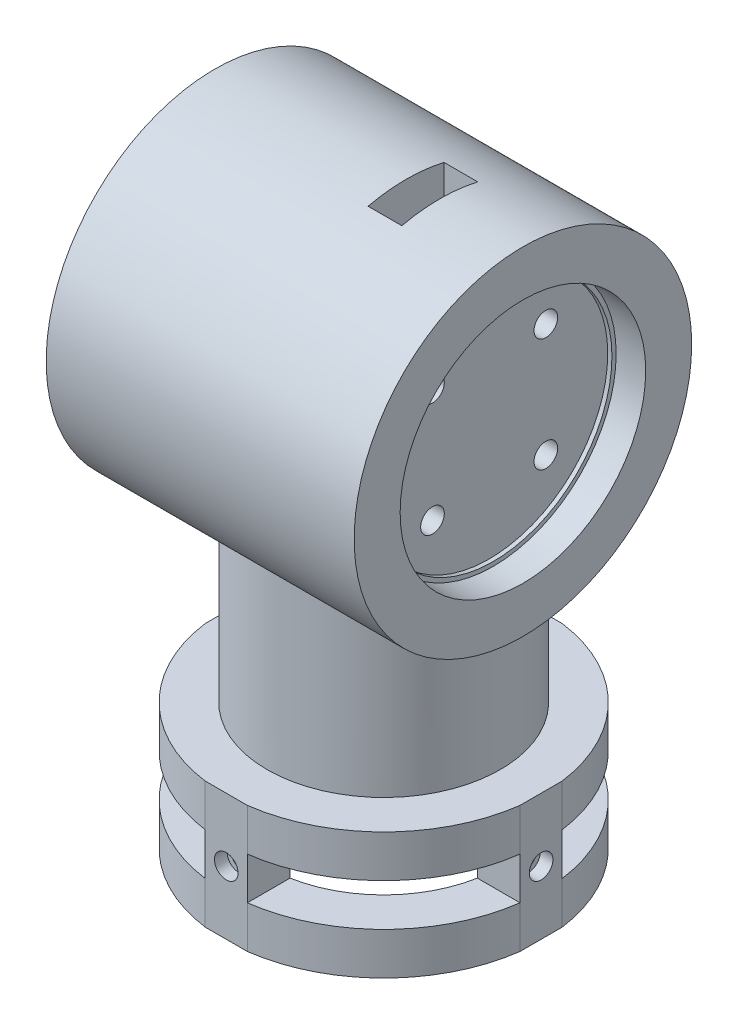
SolidWorks part; units mm, degrees
ref_plane "前视基准面" through (0, 0, 0) normal (0, 0, 1) x (1, 0, 0)
ref_plane "上视基准面" through (0, 0, 0) normal (0, 1, 0) x (1, 0, 0)
ref_plane "右视基准面" through (0, 0, 0) normal (1, 0, 0) x (0, 0, -1)
sketch "草图1" plane through (0, 0, 0) normal (0, 1, 0) x (1, 0, 0)
  circle A0 centre (0, 0) radius 27.65
  circle A2 centre (0, 0) radius 17.65
extrude "凸台-拉伸1" add sketch "草图1" along normal blind 100
sketch "草图9" plane through (0, 0, 0) normal (0, 1, 0) x (1, 0, 0)
  circle A0 centre (0, 0) radius 27.65
  circle A1 centre (0, 0) radius 37.65
extrude "凸台-拉伸6" add sketch "草图9" along normal blind 30
sketch "草图16" plane through (0, 0, 0) normal (1, 0, 0) x (0, 0, -1)
  line L0 (27.65, 100) -> (-27.65, 100) construction
  circle A0 centre (0, 100) radius 28.5
  circle A1 centre (0, 100) radius 40
extrude "凸台-拉伸8" add sketch "草图16" along normal blind 40 and the other way blind 40
sketch "草图17" plane through (0, 0, 0) normal (1, 0, 0) x (0, 0, -1)
  line L0 (27.65, 100) -> (-27.65, 100) construction
  circle A0 centre (0, 100) radius 28.5
extrude "切除-拉伸5" cut sketch "草图17" against normal through all both and the other way through all
sketch "草图19" plane through (0, 0, 0) normal (0, -1, 0) x (1, 0, 0)
  circle A0 centre (0, 0) radius 17.65
extrude "切除-拉伸6" cut sketch "草图19" against normal up to next and the other way through all
sketch "草图20" plane through (0, 0, 0) normal (1, 0, 0) x (0, 0, -1)
  circle A0 centre (0, 100) radius 28.5
extrude "凸台-拉伸9" add sketch "草图20" along normal blind 16.7 from offset 13.3
sketch "草图21" plane through (0, 0, 0) normal (0, 1, 0) x (1, 0, 0)
  line L0 (40, 0) -> (40, 9) construction
  line L1 (40, 9) -> (13.3, 9) construction
  line L4 (0, 0) -> (40, 0) construction
  line L9 (40, -40) -> (40, 40) construction
  line L17 (13.3, 9) -> (5.3, 9)
  line L18 (13.3, 9) -> (13.3, -9)
  line L19 (13.3, -9) -> (5.3, -9)
  line L20 (5.3, 9) -> (5.3, -9)
  dimension "D1" = 26.7
  dimension "D2" = 8
  dimension "D3" = 18
extrude "切除-拉伸7" cut sketch "草图21" along normal up to next
sketch "草图24" plane through (0, 0, 0) normal (1, 0, 0) x (0, 0, -1)
  circle A0 centre (0, 100) radius 28.5
  circle A1 centre (0, 100) radius 28
extrude "凸台-拉伸10" add sketch "草图24" along normal up to surface (40 mm away) from surface up to face at (40, 100, -40) starting at face at (30, 100, -28.5)
sketch "草图25" plane through (40, 0, 0) normal (1, 0, 0) x (0, 0, -1)
  circle A0 centre (0, 100) radius 40
extrude "切除-拉伸8" cut sketch "草图25" against normal blind 7
sketch "草图26" plane through (0, 0, 0) normal (0, 1, 0) x (1, 0, 0)
  line L0 (-5, 5) -> (-27.1942, 5) construction
  line L1 (-5, -5) -> (5, -5) construction
  line L2 (-5, -5) -> (-5, 5) construction
  line L3 (-5, 5) -> (5, 5) construction
  line L4 (5, -5) -> (5, 5) construction
  line L5 (-5, -5) -> (5, 5) construction
  line L6 (-5, 5) -> (5, -5) construction
  line L7 (-27.1942, 5) -> (-37.3165, 5)
  line L8 (-5, 5) -> (-5, 27.1942) construction
  line L9 (-5, 27.1942) -> (-5, 37.3165)
  line L10 (5, 5) -> (5, 27.1942) construction
  line L11 (5, 27.1942) -> (5, 37.3165)
  line L12 (5, 5) -> (27.1942, 5) construction
  line L13 (27.1942, 5) -> (37.3165, 5)
  line L14 (-5, -5) -> (-27.1942, -5) construction
  line L15 (-27.1942, -5) -> (-37.3165, -5)
  line L16 (-5, -5) -> (-5, -27.1942) construction
  line L17 (-5, -27.1942) -> (-5, -37.3165)
  line L18 (5, -5) -> (5, -27.1942) construction
  line L19 (5, -27.1942) -> (5, -37.3165)
  line L20 (5, -5) -> (27.1942, -5) construction
  line L21 (27.1942, -5) -> (37.3165, -5)
  arc A0 (-37.3165, -5) -> (-5, -37.3165) centre (0, 0) ccw
  arc A1 (-27.1942, -5) -> (-5, -27.1942) centre (0, 0) ccw
  arc A2 (-5, 27.1942) -> (-27.1942, 5) centre (0, 0) ccw
  arc A3 (-5, 37.3165) -> (-37.3165, 5) centre (0, 0) ccw
  arc A4 (27.1942, 5) -> (5, 27.1942) centre (0, 0) ccw
  arc A5 (37.3165, 5) -> (5, 37.3165) centre (0, 0) ccw
  arc A6 (5, -27.1942) -> (27.1942, -5) centre (0, 0) ccw
  arc A7 (5, -37.3165) -> (37.3165, -5) centre (0, 0) ccw
  dimension "D1" = 10
  dimension "D2" = 10
extrude "切除-拉伸9" cut sketch "草图26" against normal blind 10 from offset 20
sketch "草图27" plane through (0, 0, 0) normal (0, 1, 0) x (1, 0, 0)
  line L0 (-5, 5) -> (-5, 27.1942) construction
  line L1 (-5, -5) -> (5, -5) construction
  line L2 (-5, -5) -> (-5, 5) construction
  line L3 (-5, 5) -> (5, 5) construction
  line L4 (5, -5) -> (5, 5) construction
  line L5 (-5, -5) -> (5, 5) construction
  line L6 (-5, 5) -> (5, -5) construction
  line L7 (-5, 27.1942) -> (5, 27.1942)
  line L8 (5, 27.1942) -> (5, 5) construction
  line L9 (5, 5) -> (27.1942, 5) construction
  line L10 (27.1942, 5) -> (27.1942, -5)
  line L11 (27.1942, -5) -> (5, -5) construction
  line L12 (5, -5) -> (5, -27.1942) construction
  line L13 (5, -27.1942) -> (-5, -27.1942)
  line L14 (-5, -27.1942) -> (-5, -5) construction
  line L15 (-5, -5) -> (-27.1942, -5) construction
  line L16 (-27.1942, -5) -> (-27.1942, 5)
  line L17 (-27.1942, 5) -> (-5, 5) construction
  arc A0 (-5, 27.1942) -> (-27.1942, 5) centre (0, 0) ccw
  arc A1 (-27.1942, -5) -> (-5, -27.1942) centre (0, 0) ccw
  arc A2 (5, -27.1942) -> (27.1942, -5) centre (0, 0) ccw
  arc A3 (27.1942, 5) -> (5, 27.1942) centre (0, 0) ccw
  dimension "D1" = 10
  dimension "D2" = 10
extrude "切除-拉伸10" cut sketch "草图27" along normal blind 20
sketch "草图28" plane through (0, 0, 0) normal (1, 0, 0) x (0, 0, -1)
  circle A0 centre (0, 100) radius 29.1
extrude "切除-拉伸11" cut sketch "草图28" against normal blind 7 from offset 33
sketch "草图29" plane through (0, 0, 0) normal (1, 0, 0) x (0, 0, -1)
  circle A0 centre (0, 100) radius 28.6
extrude "切除-拉伸12" cut sketch "草图29" against normal through all from offset 13.3
sketch "草图30" plane through (0, 0, 0) normal (0, 1, 0) x (1, 0, 0)
  line L1 (5, -5) -> (-5, -5) construction
  line L2 (5, -5) -> (5, 5) construction
  line L3 (5, 5) -> (-5, 5) construction
  line L4 (-5, -5) -> (-5, 5) construction
  line L5 (5, -5) -> (-5, 5) construction
  line L6 (5, 5) -> (-5, -5) construction
  line L7 (5, 37.3165) -> (-5, 37.3165)
  line L10 (-37.3165, 5) -> (-37.3165, -5)
  line L13 (-5, -37.3165) -> (5, -37.3165)
  line L16 (37.3165, -5) -> (37.3165, 5)
  arc A0 (5, 37.3165) -> (-5, 37.3165) centre (0, 0) ccw
  arc A1 (-37.3165, 5) -> (-37.3165, -5) centre (0, 0) ccw
  arc A2 (-5, -37.3165) -> (5, -37.3165) centre (0, 0) ccw
  arc A3 (37.3165, -5) -> (37.3165, 5) centre (0, 0) ccw
  dimension "D1" = 10
  dimension "D2" = 10
extrude "切除-拉伸13" cut sketch "草图30" against normal blind 30 from offset 30
sketch "草图31" plane through (26, 0, 0) normal (1, 0, 0) x (0, 0, -1)
  circle A0 centre (0, 100) radius 28.1
extrude "切除-拉伸14" cut sketch "草图31" against normal blind 1
sketch "草图32" plane through (37.3165, 0, 0) normal (1, 0, 0) x (0, 0, -1)
  line L0 (-5, 20) -> (5, 10) construction
  point P4 (0, 15)
hole_wizard "M3 六角头螺栓的柱形沉头孔1" positions "草图32" profile "草图33" counterbore size "M3" standard "GB" end condition up to next
sketch "草图33" plane through (37.3165, 15, 0) normal (0, 1, 0) x (0, 0, -1)
  line L0 (0, 0) -> (0, 10.1224)
  line L1 (0, 10.1224) -> (1.6, 10.1224)
  line L3 (1.6, 10.1224) -> (1.6, 3)
  line L4 (1.6, 3) -> (2.8, 3)
  line L5 (2.8, 3) -> (2.8, 0)
  line L7 (2.8, 0) -> (0, 0)
  line L11 (0, -6.35) -> (0, 107.95) construction
  dimension "通孔孔直径" = 3.2
  dimension "通孔孔深度" = 10.1224
  dimension "柱形沉头孔直径" = 5.6
  dimension "柱形沉头孔深度" = 3
pattern_circular "阵列(圆周)1" count 4 every 90 about axis through (0, 100, 0) along (0, -1, 0) of "M3 六角头螺栓的柱形沉头孔1"
sketch "草图34" plane through (25, 0, 0) normal (1, 0, 0) x (0, 0, -1)
  line L1 (13.435, 113.435) -> (-13.435, 113.435) construction
  line L2 (-13.435, 113.435) -> (-13.435, 86.565) construction
  line L3 (-13.435, 86.565) -> (13.435, 86.565) construction
  line L4 (13.435, 86.565) -> (13.435, 113.435) construction
  circle A0 centre (0, 100) radius 19 construction
  circle A1 centre (0, 100) radius 13.435 construction
  point P9 (-13.435, 113.435)
  point P10 (13.435, 113.435)
  point P11 (13.435, 86.565)
  point P12 (-13.435, 86.565)
hole_wizard "M3 六角头螺栓的柱形沉头孔2" positions "草图34" profile "草图35" counterbore size "M3" standard "GB" end condition up to next
sketch "草图35" plane through (25, 86.565, 13.435) normal (0, 1, 0) x (0, 0, -1)
  line L0 (0, 0) -> (0, 11.7)
  line L1 (0, 11.7) -> (1.6, 11.7)
  line L3 (1.6, 11.7) -> (1.6, 5.7)
  line L4 (1.6, 5.7) -> (2.8, 5.7)
  line L5 (2.8, 5.7) -> (2.8, 0)
  line L7 (2.8, 0) -> (0, 0)
  line L11 (0, -6.35) -> (0, 107.95) construction
  dimension "通孔孔直径" = 3.2
  dimension "通孔孔深度" = 11.7
  dimension "柱形沉头孔直径" = 5.6
  dimension "柱形沉头孔深度" = 5.7
